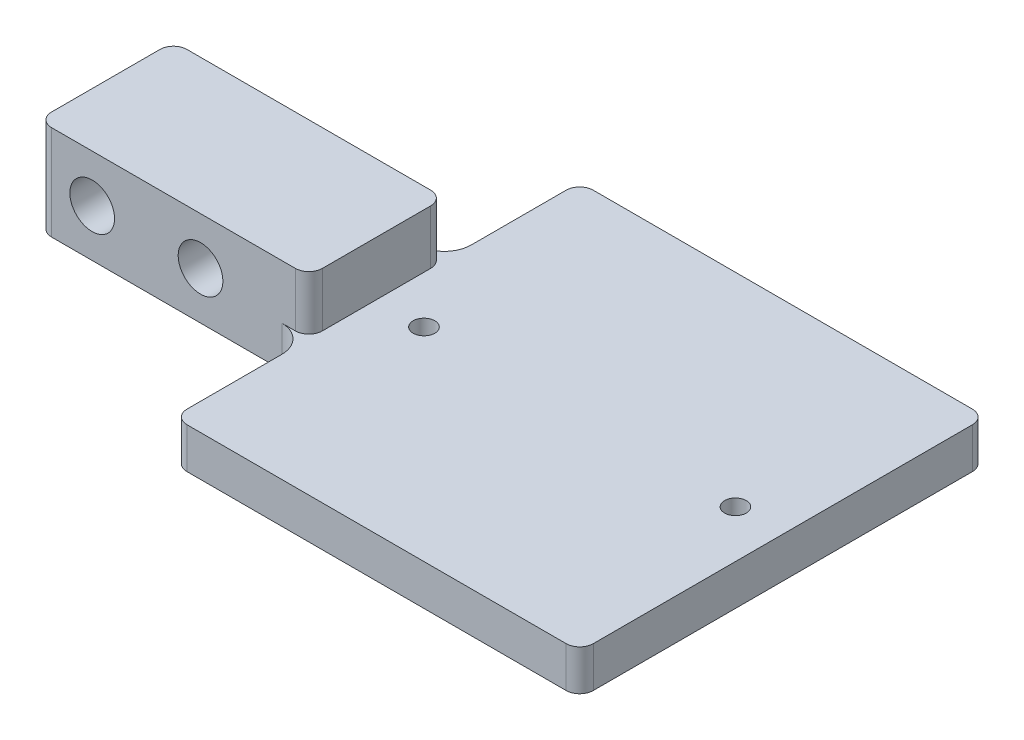
SolidWorks part; units mm, degrees
material "Brass"
ref_plane "Front Plane" through (0, 0, 0) normal (0, 0, 1) x (1, 0, 0)
ref_plane "Top Plane" through (0, 0, 0) normal (0, 1, 0) x (1, 0, 0)
ref_plane "Right Plane" through (0, 0, 0) normal (1, 0, 0) x (0, 0, -1)
sketch "Sketch1" plane through (0, 0, 0) normal (0, 1, 0) x (1, 0, 0)
  line L1 (0, 0) -> (30, 0)
  line L2 (0, 0) -> (0, 15)
  line L3 (0, 15) -> (30, 15)
  line L4 (30, 0) -> (30, 15)
  dimension "D1" = 15
  dimension "D2" = 30
extrude "Boss-Extrude1" add sketch "Sketch1" along normal blind 3
sketch "Sketch2" plane through (0, 0, 0) normal (-1, 0, 0) x (0, 0, 1)
  line L0 (-15, 0) -> (0, 0) construction
  line L1 (-10, 0) -> (-15, 0)
  line L2 (-10, 0) -> (-10, 7)
  line L3 (-10, 7) -> (-15, 7)
  line L4 (-15, 0) -> (-15, 7)
  dimension "D1" = 5
  dimension "D2" = 7
extrude "Boss-Extrude2" add sketch "Sketch2" along normal blind 20
sketch "Sketch3" plane through (-20, 0, 0) normal (-1, 0, 0) x (0, 0, 1)
  line L1 (-15, 1) -> (-15, 6)
  arc A0 (-15, 1) -> (-15, 6) centre (-15, 3.5) ccw
  dimension "D1" = 5
  dimension "D2" = 3.5
extrude "Cut-Extrude1" cut sketch "Sketch3" against normal blind 18
sketch "Sketch4" plane through (0, 3, 0) normal (0, 1, 0) x (1, 0, 0)
  line L0 (30, 15) -> (0, 15) construction
  line L1 (25.7, 15) -> (27.3, 15)
  line L2 (2.7, 15) -> (4.3, 15)
  line L3 (30, 0) -> (30, 15) construction
  line L4 (0, 15) -> (0, 10) construction
  arc A0 (25.7, 15) -> (27.3, 15) centre (26.5, 15) ccw
  arc A1 (2.7, 15) -> (4.3, 15) centre (3.5, 15) ccw
  dimension "D1" = 0.8
  dimension "D2" = 0.8
  dimension "D3" = 3.5
  dimension "D4" = 3.5
mirror "Mirror1" about plane through (0, 3, -15) normal (0, 0, 1) of bodies 103 104
sketch "Sketch5" plane through (0, 0, -10) normal (0, 0, 1) x (1, 0, 0)
  line L0 (-20, 0) -> (-20, 7) construction
  line L2 (-20, 7) -> (0, 7) construction
  circle A0 centre (-16, 3.5) radius 1.65
  circle A1 centre (-8, 3.5) radius 1.65
  dimension "D1" = 3.3
  dimension "D2" = 3.3
  dimension "D3" = 4
  dimension "D5" = 3.5
  dimension "D6" = 3.5
  dimension "D4" = 8
fillet "Fillet2" radius 2 2 edges at (0, 1.5, -10) (0, 1.5, -20)
fillet "Fillet3" radius 1 8 edges at (30, 1.5, 0) (0, 1.5, 0) (0, 1.5, -30) (30, 1.5, -30) (0, 5, -20) (0, 5, -10) (-20, 3.5, -10) (-20, 3.5, -20)
hole_wizard "M2x0.4 Tapped Hole1" positions "3DSketch1" profile "Sketch7" tap size "M2x0.4" standard "BSI" end condition through all
sketch3d "3DSketch1"
  point P0 (3.5, 3, -15)
  point P3 (26.5, 3, -15)
sketch "Sketch7" plane through (3.5, 3, -15) normal (1, 0, 0) x (0, 0, 1)
  line L0 (0, 0) -> (0, 3)
  line L1 (0, 3) -> (0.8, 3)
  line L2 (0.8, 3) -> (0.8, 0)
  line L5 (0.8, 0) -> (0, 0)
  line L11 (0, -6.35) -> (0, 107.95) construction
  dimension "Thru Tap Drill Dia." = 1.6
  dimension "Thru Tap Drill Depth" = 3
cosmetic thread "Hole Thread1" parameters "D2"=2
cosmetic thread "Hole Thread2" parameters "D2"=2
hole_wizard "M4x0.7 Tapped Hole1" positions "3DSketch2" profile "Sketch8" tap size "M4x0.7" standard "BSI" end condition through all
sketch3d "3DSketch2"
  point P0 (-16, 3.5, -10)
  point P3 (-8, 3.5, -10)
sketch "Sketch8" plane through (-16, 3.5, -10) normal (1, 0, 0) x (0, -1, 0)
  line L0 (0, 0) -> (0, 20)
  line L1 (0, 20) -> (1.65, 20)
  line L2 (1.65, 20) -> (1.65, 0)
  line L5 (1.65, 0) -> (0, 0)
  line L11 (0, -6.35) -> (0, 107.95) construction
  dimension "Thru Tap Drill Dia." = 3.3
  dimension "Thru Tap Drill Depth" = 20
cosmetic thread "Hole Thread3" parameters "D2"=4
cosmetic thread "Hole Thread4" parameters "D2"=4
equation "\"D2@Sketch4\"=\"D1@Sketch4\""
equation "\"D4@Sketch4\"=\"D3@Sketch4\""
equation "\"D2@Sketch5\"=\"D1@Sketch5\""
equation "\"D6@Sketch5\"=\"D5@Sketch5\""
